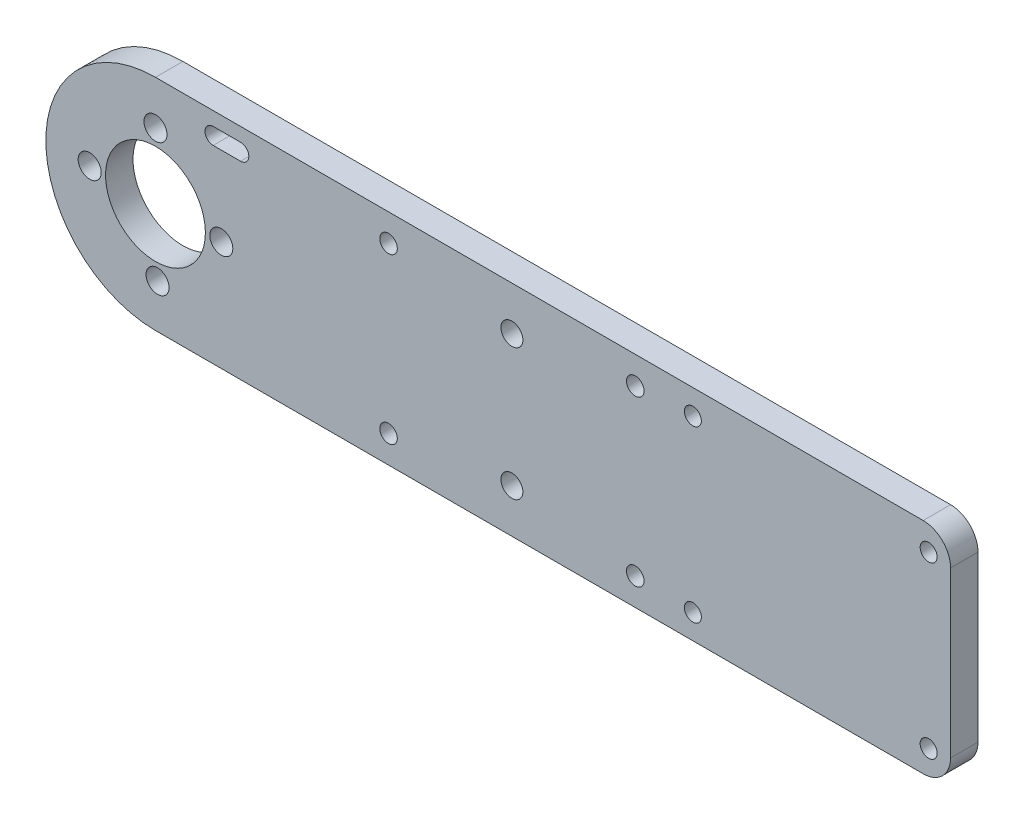
SolidWorks part; units mm, degrees
material "Acrylic (Medium-high impact)"
ref_plane "Front Plane" through (0, 0, 0) normal (0, 0, 1) x (1, 0, 0)
ref_plane "Top Plane" through (0, 0, 0) normal (0, 1, 0) x (1, 0, 0)
ref_plane "Right Plane" through (0, 0, 0) normal (1, 0, 0) x (0, 0, -1)
sketch "Sketch2" plane through (0, 0, 0) normal (0, 0, 1) x (1, 0, 0)
  line L0 (0, 20) -> (0, -20)
  line L1 (0, 20) -> (145, 20)
  line L2 (0, -20) -> (145, -20)
  line L3 (145, 20) -> (145, -20)
  line L4 (0, 0) -> (-20, 0)
  circle A0 centre (0, 0) radius 20
  circle A1 centre (0, 0) radius 9.1
  dimension "D1" = 40
  dimension "D3" = 18.2
  dimension "D2" = 165
extrude "Boss-Extrude1" add sketch "Sketch2" along normal mid plane 5 contours A1 L0 A0 | A0 L2 L3 L1 | A1 L4 A0 L0 | A1 L0 A0 L4 region at (9.696, 0, 0) region at (80.2769, 0, 0) region at (-9.696, 9.696, 0) region at (-9.696, -9.696, 0)
fillet "Fillet1" radius 5 2 edges at (145, -20, 0) (145, 20, 0)
sketch "Sketch3" plane through (0, 0, -2.5) normal (0, 0, -1) x (-1, 0, 0)
  line L0 (-119.5, 20) -> (-119.5, -20)
  line L1 (-119.5, 0) -> (-98, 0)
  line L2 (-98, 0) -> (-98, 15.5)
  line L3 (-145, 15) -> (-145, -15)
  line L4 (-140, -20) -> (0, -20)
  line L5 (0, 20) -> (-140, 20)
  line L6 (-145, 15) -> (-145, -15)
  line L7 (-140, -20) -> (0, -20)
  line L8 (0, 20) -> (-140, 20)
  line L9 (-119.5, 0) -> (-65, 0)
  line L10 (-65, 0) -> (-65, 15)
  line L11 (-65, 15) -> (-87.5, 15)
  line L12 (0, 0) -> (0, 12)
  line L13 (0, 0) -> (-65, 0)
  line L14 (-15.5185, 16) -> (-10.5185, 16) construction
  line L17 (-15.5185, 17.5) -> (-10.5185, 17.5)
  line L18 (-15.5185, 14.5) -> (-10.5185, 14.5)
  line L19 (0, 0) -> (18.4819, 0)
  line L20 (-65, 0.6163) -> (-65, 6.1951)
  line L21 (-65, 0) -> (-65, 12)
  circle A0 centre (0, 0) radius 12
  circle A1 centre (-98, 15.5) radius 1.55
  circle A2 centre (-98, -15.5) radius 1.55
  arc A3 (-145, -15) -> (-140, -20) centre (-140, -15) ccw
  arc A4 (0, -20) -> (0, 20) centre (0, 0) ccw
  arc A5 (-140, 20) -> (-145, 15) centre (-140, 15) ccw
  arc A6 (-145, -15) -> (-140, -20) centre (-140, -15) ccw
  arc A7 (0, -20) -> (0, 20) centre (0, 0) ccw
  arc A8 (-140, 20) -> (-145, 15) centre (-140, 15) ccw
  circle A9 centre (-141, -15.5) radius 1.55
  circle A10 centre (-141, 15.5) radius 1.55
  circle A11 centre (-87.5, 15) radius 1.6
  circle A12 centre (-87.5, -15) radius 1.6
  circle A13 centre (-42.5, -15) radius 1.6
  circle A14 centre (-42.5, 15) radius 1.6
  circle A15 centre (0, 12) radius 2.1
  circle A16 centre (12, 0) radius 2.1
  circle A17 centre (-0.3765, -12) radius 2.1
  circle A18 centre (-12, 0) radius 2.1
  arc A21 (-15.5185, 17.5) -> (-15.5185, 14.5) centre (-15.5185, 16) ccw
  arc A22 (-10.5185, 14.5) -> (-10.5185, 17.5) centre (-10.5185, 16) ccw
  circle A23 centre (-65, 12) radius 2
  circle A25 centre (-65, -12) radius 2
  point P35 (-13.0185, 16)
  point P48 (12, 0)
  point P53 (-12, 0)
  point P54 (-0.3765, -12)
  dimension "D2" = 24
  dimension "D6" = 3.1
  dimension "D10" = 3.2
  dimension "D11" = 4.2
  dimension "D13" = 65
  dimension "D17" = 65
  dimension "D18" = 4.2
  dimension "D12" = 4.2
  dimension "D19" = 4.2
  dimension "D21" = 4
  dimension "D3" = 21.5
  dimension "D4" = 15.5
  dimension "D5" = 98
  dimension "D7" = 27
  dimension "D8" = 15
  dimension "D9" = 22.5
  dimension "D14" = 5
  dimension "D15" = 3
  dimension "D16" = 4
  dimension "D20" = 12
  dimension "D1" = 0
extrude "Cut-Extrude1" cut sketch "Sketch3" against normal through all contours L19 A16 A0 | A0 A16 L19 | L19 A16 A0 | A0 A16 L19 | A0 A15 | A0 A15 L12 | L12 A15 A0 | A0 A18 L13 | L13 A18 A0 | A0 A18 L13 | L13 A18 A0 | A0 A17 | A0 A17 region at (12.8574, 0.9157, -2.5) region at (12.8574, -0.9157, -2.5) region at (11.0765, 0.8649, -2.5) region at (11.0765, -0.8649, -2.5) region at (0, 12.8574, -2.5) region at (0.8649, 11.0765, -2.5) region at (0.3474, -11.0737, -2.5) region at (0.4033, -12.8538, -2.5) region at (-0.8649, 11.0765, -2.5) region at (-11.0765, 0.8649, -2.5) region at (-11.0765, -0.8649, -2.5) region at (-12.8574, -0.9157, -2.5) region at (-12.8574, 0.9157, -2.5)
extrude "Cut-Extrude2" cut sketch "Sketch3<4>" against normal blind 10 contours L18 A22 L17 A21 | A12 | A11 | A13 | A14 | A10 | A9 | A1 | A2 | L21 A23 L10 | L10 A23 L21 | A25 region at (99.065, 16.565, -2.5) region at (89.0547, 15, -2.5) region at (65.8488, 12, -2.5) region at (64.1512, 12, -2.5) region at (13.0185, 16, -2.5) region at (98, -15.5, -2.5) region at (141, -15.5, -2.5) region at (141, 15.5, -2.5) region at (87.5, -15, -2.5) region at (42.5, -15, -2.5) region at (42.5, 15, -2.5) region at (65, -12, -2.5)
sketch "Sketch3<4>" plane through (0, 0, -2.5) normal (0, 0, -1) x (-1, 0, 0) same geometry as "Sketch3"
sketch "Sketch4" plane through (0, 0, -2.5) normal (0, 0, -1) x (-1, 0, 0)
  circle A0 centre (-42.5, 15) radius 2.5
  circle A1 centre (-42.5, -15) radius 2.5
  dimension "D1" = 5
  dimension "D2" = 5
extrude "Cut-Extrude3" cut sketch "Sketch4" against normal blind 2
